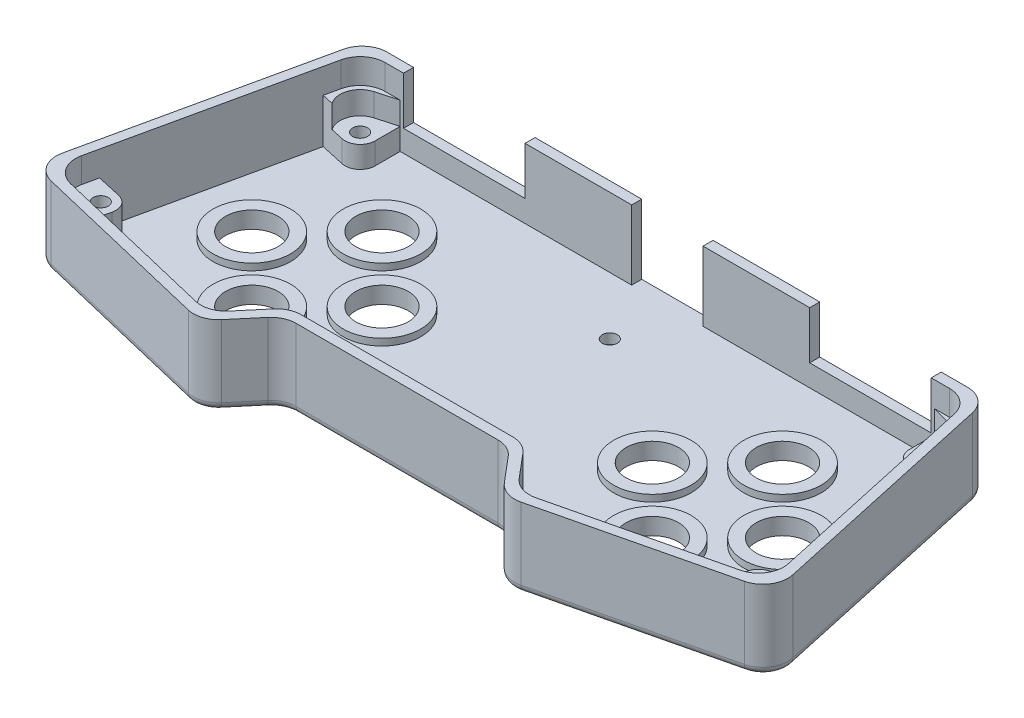
SolidWorks part; units mm, degrees
ref_plane "Front Plane" through (0, 0, 0) normal (0, 0, 1) x (1, 0, 0)
ref_plane "Top Plane" through (0, 0, 0) normal (0, 1, 0) x (1, 0, 0)
ref_plane "Right Plane" through (0, 0, 0) normal (1, 0, 0) x (0, 0, -1)
sketch "Sketch10" plane through (0, 0, 0) normal (0, 1, 0) x (1, 0, 0)
  line L0 (62, 32) -> (-62, 32)
  line L1 (-62, 32) -> (-74, -22.6992)
  line L2 (-74, -22.6992) -> (-30.236, -33.1736)
  line L3 (-30.236, -33.1736) -> (-22.5, -24)
  line L4 (-22.5, -24) -> (22.5, -24)
  line L5 (22.5, -24) -> (30.236, -33.1736)
  line L6 (30.236, -33.1736) -> (74, -22.6992)
  line L7 (74, -22.6992) -> (62, 32)
  line L8 (40, 13) -> (40, -13) construction
  line L9 (27, 0) -> (53, 0) construction
  line L10 (-40, 13) -> (-40, -13) construction
  line L11 (-53, 0) -> (-27, 0) construction
  line L12 (-27, 0) -> (27, 0) construction
  line L13 (0, 0) -> (0, 32) construction
  line L14 (0, 0) -> (0, -24) construction
  line L15 (74, -22.6992) -> (22.5, -24) construction
  line L16 (-22.5, -24) -> (-74, -22.6992) construction
  circle A0 centre (40, 13) radius 5.25
  circle A1 centre (27, 0) radius 5.25
  circle A2 centre (40, -13) radius 5.25
  circle A3 centre (53, 0) radius 5.25
  circle A4 centre (-40, 13) radius 5.25
  circle A5 centre (-53, 0) radius 5.25
  circle A6 centre (-40, -13) radius 5.25
  circle A7 centre (-27, 0) radius 5.25
  point P16 (40, 0)
  point P17 (-40, 0)
  dimension "D1" = 10.5
  dimension "D2" = 26
  dimension "D3" = 56
  dimension "D4" = 124
  dimension "D5" = 80
  dimension "D6" = 148
  dimension "D7" = 56
  dimension "D8" = 45
  dimension "D9" = 32
  dimension "D10" = 45
  dimension "D11" = 12
extrude "Boss-Extrude5" add sketch "Sketch10" along normal blind 2 separate body
sketch "Sketch11" plane through (0, 2, 0) normal (0, 1, 0) x (1, 0, 0)
  line L0 (-74, -22.6992) -> (-62, 32)
  line L1 (-62, 32) -> (62, 32)
  line L2 (62, 32) -> (74, -22.6992)
  line L3 (74, -22.6992) -> (30.236, -33.1736)
  line L4 (30.236, -33.1736) -> (22.5, -24)
  line L5 (22.5, -24) -> (-22.5, -24)
  line L6 (-22.5, -24) -> (-30.236, -33.1736)
  line L7 (-30.236, -33.1736) -> (-74, -22.6992)
  line L8 (-30.9699, -30.9414) -> (-71.6259, -21.2109)
  line L9 (-71.6259, -21.2109) -> (-60.3912, 30)
  line L10 (-60.3912, 30) -> (60.3912, 30)
  line L11 (60.3912, 30) -> (71.6259, -21.2109)
  line L12 (71.6259, -21.2109) -> (30.9699, -30.9414)
  line L13 (30.9699, -30.9414) -> (23.4296, -22)
  line L14 (23.4296, -22) -> (-23.4296, -22)
  line L15 (-23.4296, -22) -> (-30.9699, -30.9414)
  dimension "D1" = 2
extrude "Boss-Extrude7" add sketch "Sketch11" along direction (0, -1, 0) on the side of the normal offset from surface (13.875 mm away) 15.875 up to face at (-40, 0, 18.25)
fillet "Fillet4" radius 5 16 edges at (62, 7.9375, -32) (74, 7.9375, 22.6992) (30.236, 7.9375, 33.1736) (22.5, 7.9375, 24) (-22.5, 7.9375, 24) (-30.236, 7.9375, 33.1736) (-62, 7.9375, -32) (-74, 7.9375, 22.6992) (71.6259, 8.9375, 21.2109) (60.3912, 8.9375, -30) (30.9699, 8.9375, 30.9414) (23.4296, 8.9375, 22) (-23.4296, 8.9375, 22) (-30.9699, 8.9375, 30.9414) (-71.6259, 8.9375, 21.2109) (-60.3912, 8.9375, -30)
fillet "Fillet5" radius 1.5 16 edges at (30.509, 0, 32.3431) (26.1233, 0, 28.2966) (22.2835, 0, 24.4659) (0, 0, 24) (-22.2835, 0, 24.4659) (-26.1233, 0, 28.2966) (-30.509, 0, 32.3431) (-51.2316, 0, 28.1485) (-72.3012, 0, 21.6342) (-67.9053, 0, -5.0822) (-61.1119, 0, -30.896) (0, 0, -32) (61.1119, 0, -30.896) (67.9053, 0, -5.0822) (72.3012, 0, 21.6342) (51.2316, 0, 28.1485)
sketch "Sketch12" plane through (0, 2, 0) normal (0, 1, 0) x (1, 0, 0)
  line L0 (-61.8959, 23.1411) -> (-57.0121, 22.0697)
  line L1 (-61.2531, 26.0714) -> (-70.5746, -16.4188) construction
  line L2 (-53.3692, 25) -> (-53.3692, 30)
  line L3 (56.3692, 30) -> (-56.3692, 30) construction
  line L4 (-53.3692, 30) -> (-56.3692, 30)
  line L5 (-61.2531, 26.0714) -> (-61.8959, 23.1411)
  line L6 (-70.5746, -16.4188) -> (-69.9318, -13.4885)
  line L7 (-69.9318, -13.4885) -> (-65.0479, -14.5599)
  line L8 (-62.7732, -18.1885) -> (-63.937, -23.0512)
  line L9 (-66.8546, -22.3529) -> (-33.9684, -30.2238) construction
  line L10 (-63.937, -23.0512) -> (-66.8546, -22.3529)
  line L11 (0, 0) -> (0, 17.9434) construction
  line L12 (63.937, -23.0512) -> (66.8546, -22.3529)
  line L13 (62.7732, -18.1885) -> (63.937, -23.0512)
  line L14 (69.9318, -13.4885) -> (65.0479, -14.5599)
  line L15 (70.5746, -16.4188) -> (69.9318, -13.4885)
  line L16 (61.2531, 26.0714) -> (61.8959, 23.1411)
  line L17 (53.3692, 30) -> (56.3692, 30)
  line L18 (53.3692, 25) -> (53.3692, 30)
  line L19 (61.8959, 23.1411) -> (57.0121, 22.0697)
  arc A0 (-57.0121, 22.0697) -> (-53.3692, 25) centre (-56.3692, 25) ccw
  arc A1 (-56.3692, 30) -> (-61.2531, 26.0714) centre (-56.3692, 25) ccw
  arc A2 (-65.0479, -14.5599) -> (-62.7732, -18.1885) centre (-65.6908, -17.4902) cw
  arc A3 (-66.8546, -22.3529) -> (-70.5746, -16.4188) centre (-65.6908, -17.4902) cw
  circle A4 centre (-56.3692, 25) radius 1.5
  circle A5 centre (-65.6908, -17.4902) radius 1.5
  circle A6 centre (65.6908, -17.4902) radius 1.5
  circle A7 centre (56.3692, 25) radius 1.5
  arc A8 (66.8546, -22.3529) -> (70.5746, -16.4188) centre (65.6908, -17.4902) ccw
  arc A9 (65.0479, -14.5599) -> (62.7732, -18.1885) centre (65.6908, -17.4902) ccw
  arc A10 (56.3692, 30) -> (61.2531, 26.0714) centre (56.3692, 25) cw
  arc A11 (57.0121, 22.0697) -> (53.3692, 25) centre (56.3692, 25) cw
  dimension "D1" = 3
  dimension "D2" = 1.5
extrude "Boss-Extrude8" add sketch "Sketch12" along normal offset from surface (8.875 mm away) 5 up to face at (0, 15.875, 10.9337)
sketch "Sketch14" plane through (0, 0, -30) normal (0, 0, 1) x (1, 0, 0)
  line L0 (-56.3692, 15.875) -> (56.3692, 15.875) construction
  line L1 (-52.7009, 15.875) -> (-28.427, 15.875)
  line L2 (-52.7009, 15.875) -> (-52.7009, 6.3348)
  line L3 (-52.7009, 6.3348) -> (-28.427, 6.3348)
  line L4 (-28.427, 15.875) -> (-28.427, 6.3348)
  line L5 (0, 0) -> (0, 15.875) construction
  line L6 (28.427, 15.875) -> (28.427, 6.3348)
  line L7 (52.7009, 6.3348) -> (28.427, 6.3348)
  line L8 (52.7009, 15.875) -> (52.7009, 6.3348)
  line L9 (52.7009, 15.875) -> (28.427, 15.875)
  line L10 (-6.625, 15.03) -> (-6.625, 2.5) construction
  line L11 (-7.125, 15.875) -> (7.125, 15.875)
  line L12 (-7.125, 15.875) -> (-7.125, 2)
  line L13 (-7.125, 2) -> (7.125, 2)
  line L14 (7.125, 15.875) -> (7.125, 2)
  line L15 (53.3692, 2) -> (-53.3692, 2) construction
  point P19 (-7.125, 1.228)
  dimension "D1" = 0.5
extrude "Cut-Extrude2" cut sketch "Sketch14" against normal through all
sketch "Sketch13" plane through (0, 10.875, 0) normal (0, 1, 0) x (1, 0, 0)
  line L0 (-57.4531, 28.8503) -> (-53.3692, 30)
  line L1 (-53.3692, 30) -> (-52.4618, 25.8555)
  line L2 (57.4531, 28.8503) -> (53.3692, 30)
  line L3 (53.3692, 30) -> (52.4618, 25.8555)
  arc A0 (-57.4531, 28.8503) -> (-52.4618, 25.8555) centre (-56.3692, 25) ccw
  arc A1 (52.4618, 25.8555) -> (57.4531, 28.8503) centre (56.3692, 25) ccw
  dimension "D1" = 8
extrude "Cut-Extrude1" cut sketch "Sketch13" against normal up to surface (4.5402 mm away) up to face at (-40.5639, 6.3348, -31)
sketch "Sketch15" plane through (0, 0, 0) normal (0, -1, 0) x (1, 0, 0)
  line L0 (0, -18.5) -> (0, -30.5) construction
  line L1 (-57.978, -30.5) -> (57.978, -30.5) construction
  circle A0 centre (0, -18.5) radius 1.5
  dimension "D2" = 3
  dimension "D1" = 12
extrude "Cut-Extrude3" cut sketch "Sketch15" against normal through all contours A0
sketch "Sketch16" plane through (0, 2, 0) normal (0, 1, 0) x (1, 0, 0)
  circle A0 centre (-40, 13) radius 7.75
  circle A1 centre (-40, 13) radius 5.25
  circle A2 centre (-27, 0) radius 7.75
  circle A3 centre (-27, 0) radius 5.25
  circle A4 centre (-53, 0) radius 5.25
  circle A5 centre (-53, 0) radius 7.75
  circle A6 centre (-40, -13) radius 5.25
  circle A7 centre (-40, -13) radius 7.75
  circle A8 centre (-40, 13) radius 5.25 construction
  circle A9 centre (-53, 0) radius 5.25 construction
  circle A10 centre (-40, -13) radius 5.25 construction
  circle A11 centre (-27, 0) radius 5.25 construction
  dimension "D1" = 2.5
extrude "Boss-Extrude9" add sketch "Sketch16" along normal blind 1.35
mirror "Mirror1" about plane through (0, 0, 0) normal (1, 0, 0) of "Boss-Extrude9"
